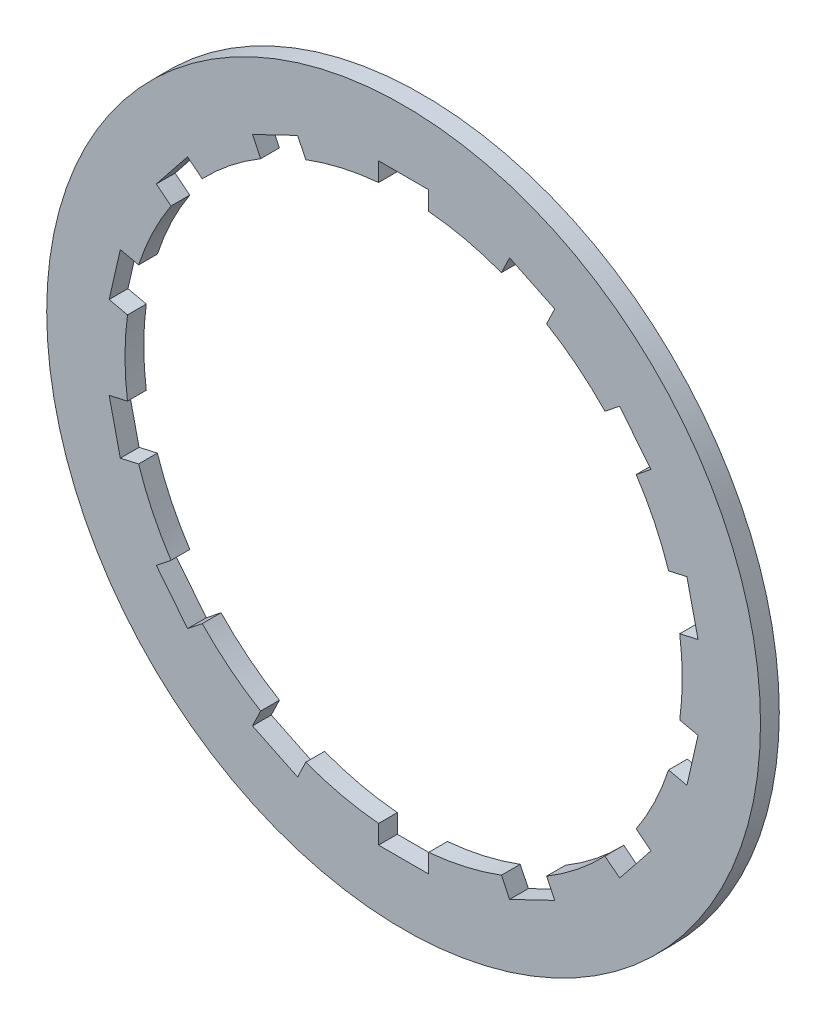
SolidWorks part; units mm, degrees
material "PETG"
ref_plane "Front Plane" through (0, 0, 0) normal (0, 0, 1) x (1, 0, 0)
ref_plane "Top Plane" through (0, 0, 0) normal (0, 1, 0) x (1, 0, 0)
ref_plane "Right Plane" through (0, 0, 0) normal (1, 0, 0) x (0, 0, -1)
sketch "Sketch1" plane through (0, 0, 0) normal (0, 0, 1) x (1, 0, 0)
  line L0 (0, 0) -> (0, 50000) construction
  circle A0 centre (0, 0) radius 57
  circle A1 centre (0, 0) radius 44.5
  dimension "D1" = 114
  dimension "D2" = 89
extrude "Boss-Extrude1" add sketch "Sketch1" along normal blind 3
sketch "Sketch3" plane through (0, 0, 3) normal (0, 0, 1) x (1, 0, 0)
  line L0 (-4, 47.3199) -> (4, 47.3199)
  line L2 (4, 47.3199) -> (4, 44.3199)
  line L3 (4, 44.3199) -> (-4, 44.3199)
  line L4 (-4, 44.3199) -> (-4, 47.3199)
  circle A0 centre (0, 0) radius 44.5 construction
  point P0 (0, 0)
  point P3 (0, 47.3199)
  dimension "D1" = 8
  dimension "D2" = 3
extrude "Cut-Extrude1" cut sketch "Sketch3" against normal up to next
pattern_circular "CirPattern1" count 14 over 360 about axis through (0, 0, 3) along (0, 0, -1) of "Cut-Extrude1" reverse direction yes
equation "\"CanSat_Len\"= 400mm"
equation "\"CanSat_Dia\"= 150mm"
equation "\"BodyTube_ID\"= 114mm"
equation "\"BodyTube_OD\"= 120mm"
equation "\"PayLoadBay_ID\"= 164mm"
equation "\"PayLoadBay_OD\"= 170mm"
equation "\"ParachuteBay_Pitch\"= 300mm"
equation "\"ElectronicsTray_PitchDist\"= 50mm"
equation "\"ElectronicsTray_Height\"= 140mm"
equation "\"MotorDia\"= 98mm"
equation "\"MotorLen\"=289mm"
equation "\"D1@Sketch1\"=\"BodyTube_ID\""
